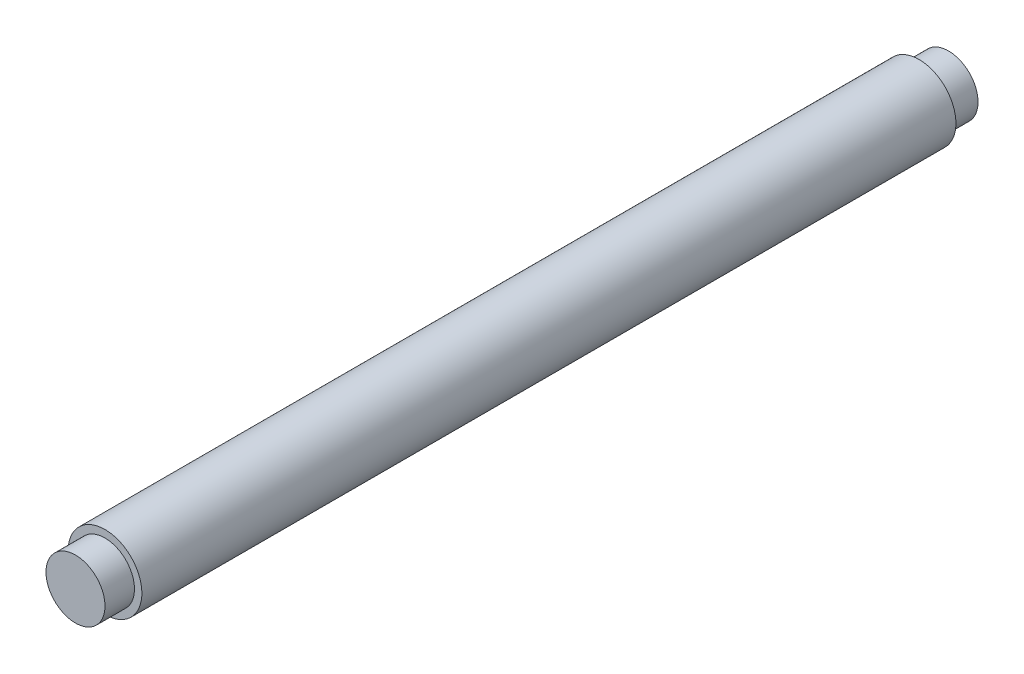
SolidWorks part; units mm, degrees
material "AISI 1020 Steel, Cold Rolled"
ref_plane "Front Plane" through (0, 0, 0) normal (0, 0, 1) x (1, 0, 0)
ref_plane "Top Plane" through (0, 0, 0) normal (0, 1, 0) x (1, 0, 0)
ref_plane "Right Plane" through (0, 0, 0) normal (1, 0, 0) x (0, 0, -1)
sketch "Sketch2" plane through (0, 0, 0) normal (0, 0, 1) x (1, 0, 0)
  circle A0 centre (0, 0) radius 7.9375
  dimension "D1" = 15.875
extrude "Boss-Extrude1" add sketch "Sketch2" along normal blind 187.96
sketch "Sketch3" [suppressed] plane through (0, 0, 220.98) normal (0, 0, 1) x (1, 0, 0)
  circle A0 centre (0, 0) radius 6.35
extrude "Cut-Extrude1" [suppressed] cut sketch "Sketch3" against normal blind 26.416
sketch "Sketch4" [suppressed] plane through (0, 0, 194.564) normal (0, 0, 1) x (1, 0, 0)
  circle A0 centre (0, 0) radius 3.175
  dimension "D1" = 6.35
extrude "Boss-Extrude2" [suppressed] add sketch "Sketch4" along normal blind 26.416
sketch "Sketch5" [suppressed] plane through (0, 0, 0) normal (0, 0, -1) x (-1, 0, 0)
  circle A0 centre (0, 0) radius 6.35
extrude "Cut-Extrude2" [suppressed] cut sketch "Sketch5" against normal blind 26.416
sketch "Sketch6" [suppressed] plane through (0, 0, 26.416) normal (0, 0, -1) x (-1, 0, 0)
  circle A0 centre (0, 0) radius 3.175
  dimension "D1" = 6.35
extrude "Boss-Extrude3" [suppressed] add sketch "Sketch6" along normal blind 26.416
sketch "Sketch7" [suppressed] plane through (0, 0, 0) normal (0, 0, -1) x (-1, 0, 0)
  circle A0 centre (0, 0) radius 14.231
extrude "Cut-Extrude3" [suppressed] cut sketch "Sketch7" against normal blind 27.432
sketch "Sketch8" [suppressed] plane through (0, 0, 27.432) normal (0, 0, -1) x (-1, 0, 0)
  circle A0 centre (0, 0) radius 3.175
  dimension "D1" = 6.35
extrude "Boss-Extrude4" [suppressed] add sketch "Sketch8" along normal blind 27.432
sketch "Sketch9" [suppressed] plane through (0, 0, 220.98) normal (0, 0, 1) x (1, 0, 0)
  circle A0 centre (0, 0) radius 8.8374
extrude "Cut-Extrude4" [suppressed] cut sketch "Sketch9" against normal blind 27.432
sketch "Sketch10" [suppressed] plane through (0, 0, 193.548) normal (0, 0, 1) x (1, 0, 0)
  circle A0 centre (0, 0) radius 3.175
  dimension "D1" = 6.35
extrude "Boss-Extrude5" [suppressed] add sketch "Sketch10" along normal blind 27.432
sketch "Sketch11" plane through (0, 0, 0) normal (0, 1, 0) x (1, 0, 0)
  line L0 (0, 0) -> (0, -187.96) construction
  line L1 (7.9375, 0) -> (6.35, 0)
  line L2 (7.9375, 0) -> (7.9375, -6.35)
  line L3 (7.9375, -6.35) -> (6.35, -6.35)
  line L4 (6.35, 0) -> (6.35, -6.35)
  line L5 (7.9375, -187.96) -> (6.35, -187.96)
  line L6 (7.9375, -187.96) -> (7.9375, -181.61)
  line L7 (7.9375, -181.61) -> (6.35, -181.61)
  line L8 (6.35, -187.96) -> (6.35, -181.61)
  dimension "D1" = 6.35
  dimension "D2" = 1.5875
revolve "Cut-Revolve1" cut sketch "Sketch11" angle 360 about L0
